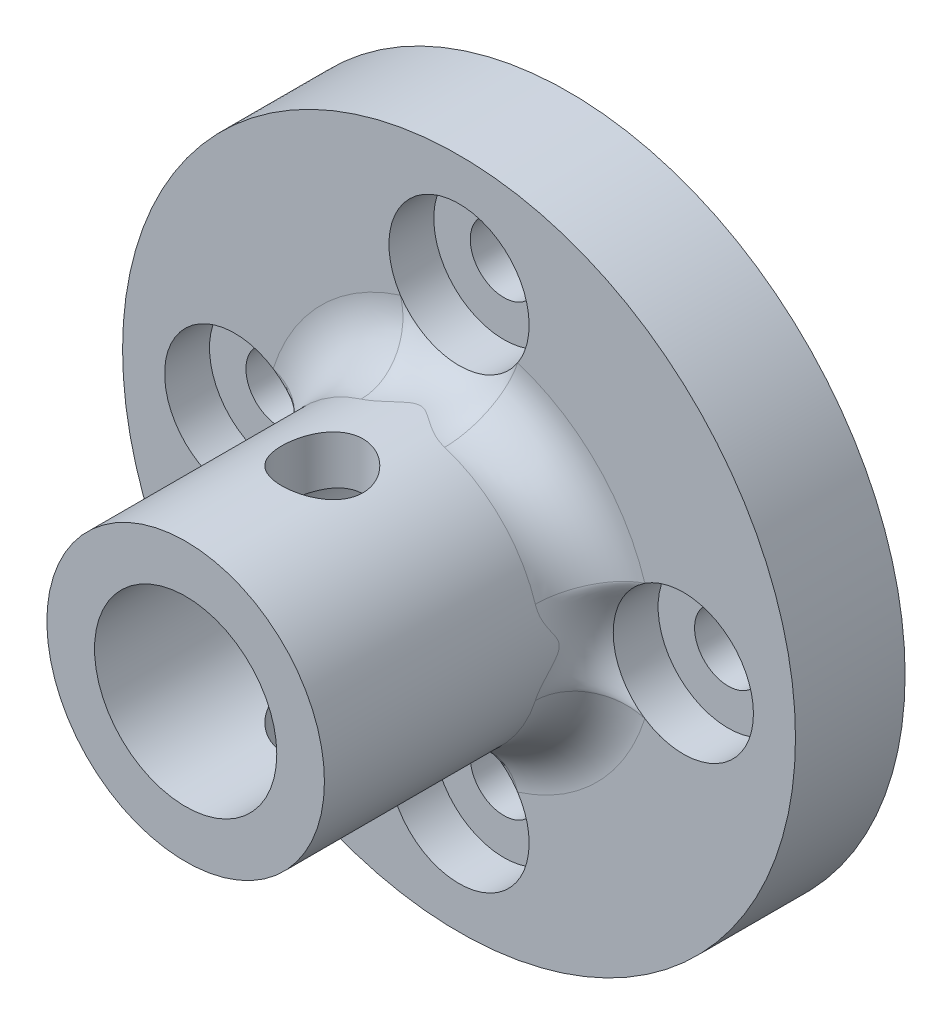
SolidWorks part; units mm, degrees
ref_plane "Plan de face" through (0, 0, 0) normal (0, 0, 1) x (1, 0, 0)
ref_plane "Plan de dessus" through (0, 0, 0) normal (0, 1, 0) x (1, 0, 0)
ref_plane "Plan de droite" through (0, 0, 0) normal (1, 0, 0) x (0, 0, -1)
sketch "Esquisse1" plane through (0, 0, 0) normal (0, 0, 1) x (1, 0, 0)
  circle A0 centre (0, 0) radius 12
  dimension "D1" = 24
extrude "Boss.-Extru.1" add sketch "Esquisse1" along normal blind 3.91
sketch "Esquisse6" plane through (0, 0, 0) normal (0, 0, -1) x (-1, 0, 0)
  circle A0 centre (0, 0) radius 4
  dimension "D1" = 8
extrude "Enlèv. mat.-Extru.2" cut sketch "Esquisse6" against normal blind 1.91
sketch "Esquisse7" plane through (0, 0, 3.91) normal (0, 0, 1) x (1, 0, 0)
  circle A1 centre (0, 0) radius 4.95
  circle A2 centre (0, 0) radius 3.25
  dimension "D1" = 6.5
  dimension "D3" = 9.9
extrude "Boss.-Extru.2" add sketch "Esquisse7" along normal blind 9.75 contours A1 | A1 region at (-4.81, 0, 3.91)
hole_wizard "Chambrage pour vis à tête ronde bombée M21" positions "Esquisse10" profile "Esquisse11" counterbore size "M2" standard "Ansi Metric" end condition through all
sketch "Esquisse10" plane through (0, 0, 3.91) normal (0, 0, 1) x (1, 0, 0)
  point P0 (0, 8)
  dimension "D1" = 8
sketch "Esquisse11" plane through (0, 8, 3.91) normal (1, 0, 0) x (0, -1, 0)
  line L0 (0, 0) -> (0, 3.91)
  line L1 (0, 3.91) -> (1.2, 3.91)
  line L3 (1.2, 3.91) -> (1.2, 1.6)
  line L4 (1.2, 1.6) -> (2.5, 1.6)
  line L5 (2.5, 1.6) -> (2.5, 0)
  line L7 (2.5, 0) -> (0, 0)
  line L11 (0, -6.35) -> (0, 107.95) construction
  dimension "Diamètre du perçage jusqu'au prochain" = 2.4
  dimension "Profondeur du perçage jusqu'au prochain" = 3.91
  dimension "Diamètre du chambrage" = 5
  dimension "Profondeur du chambrage" = 1.6
pattern_circular "Répétition circulaire2" count 4 every 90 about axis through (0, 0, 3.91) along (0, 0, 1) of "Chambrage pour vis à tête ronde bombée M21"
sketch "Esquisse12" plane through (0, 0, 0) normal (0, 1, 0) x (1, 0, 0)
  line L0 (0, -3.91) -> (0, -13.66) construction
  line L1 (-4.95, -3.91) -> (4.95, -3.91) construction
  line L2 (-4.95, -13.66) -> (4.95, -13.66) construction
  circle A0 centre (0, -8.785) radius 1.45
  point P8 (0, -8.785)
  dimension "D1" = 2.9
extrude "Enlèv. mat.-Extru.3" cut sketch "Esquisse12" against normal through all both and the other way through all
fillet "Congé1" radius 2 1 edges at (4.95, 0, 3.91)
